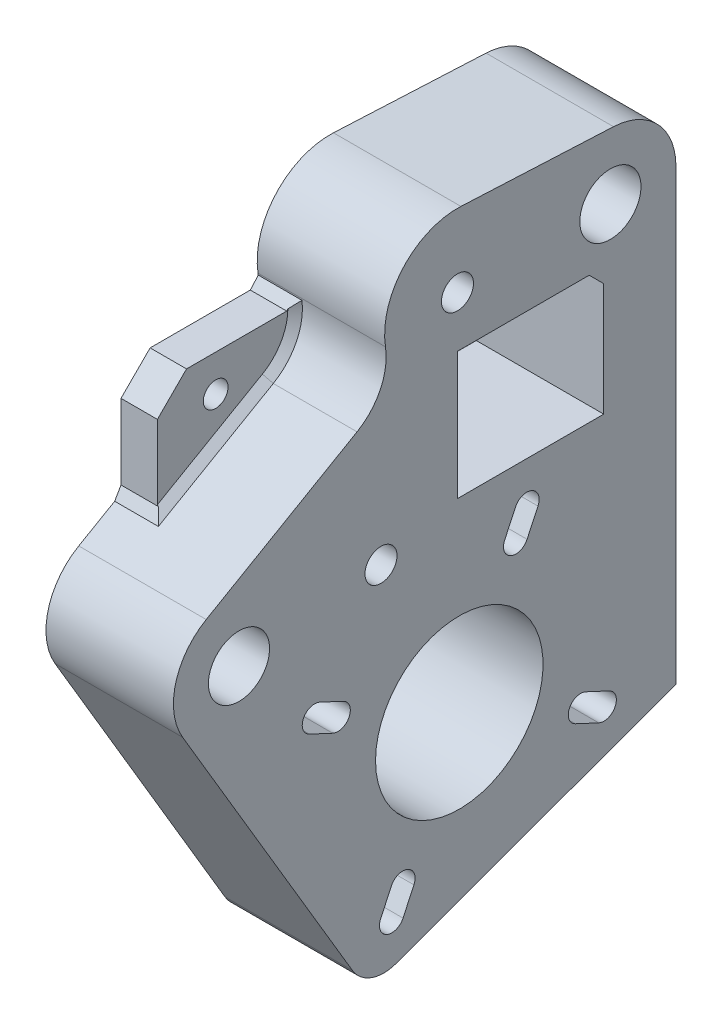
SolidWorks part; units mm, degrees
ref_plane "Front Plane" through (0, 0, 0) normal (0, 0, 1) x (1, 0, 0)
ref_plane "Top Plane" through (0, 0, 0) normal (0, 1, 0) x (1, 0, 0)
ref_plane "Right Plane" through (0, 0, 0) normal (1, 0, 0) x (0, 0, -1)
ref_plane "Plane1" through (0, 0, 0) normal (-1, 0, 0) x (0, -1, 0)
sketch "Sketch1" plane through (0, 0, 0) normal (-1, 0, 0) x (0, -1, 0)
  line L0 (11.2005, 72.3805) -> (-8.7575, 37.8123)
  line L1 (-24.9887, 29.5238) -> (-23.5812, 0)
  line L2 (-23.5812, 0) -> (46.6053, 0)
  line L3 (46.6053, 0) -> (62.0013, 42.3)
  line L4 (62.0013, 42.3) -> (11.2005, 72.3805)
  arc A0 (-8.7575, 37.8123) -> (-24.9887, 29.5238) centre (-15, 30) ccw
extrude "Boss-Extrude1" add sketch "Sketch1" against normal blind 17.5
sketch "Sketch2" plane through (0, 0, 0) normal (-1, 0, 0) x (0, -1, 0)
  line L0 (-8.7575, 37.8123) -> (3.302, 58.7)
  line L1 (3.302, 58.7) -> (-12, 58.7)
  line L2 (-12, 58.7) -> (-12, 39.5394)
  arc A0 (-12, 39.5394) -> (-8.7575, 37.8123) centre (-15, 30) cw
extrude "Boss-Extrude2" add sketch "Sketch2" against normal blind 5
sketch "Sketch3" plane through (0, 0, 0) normal (-1, 0, 0) x (0, 0, 1)
  line L0 (18.9442, -15.9372) -> (20.4384, -19.1415)
  line L1 (23.5198, -17.7046) -> (22.0256, -14.5003)
  arc A0 (20.4384, -19.1415) -> (23.5198, -17.7046) centre (21.9791, -18.423) ccw
  arc A1 (22.0256, -14.5003) -> (18.9442, -15.9372) centre (20.4849, -15.2188) ccw
extrude "Cut-Extrude1" cut sketch "Sketch3" against normal through all
sketch "Sketch4" plane through (0, 0, 0) normal (-1, 0, 0) x (0, 0, 1)
  line L0 (48.8969, -24.2807) -> (45.6927, -25.7748)
  line L1 (47.1296, -28.8563) -> (50.3338, -27.3621)
  arc A0 (50.3338, -27.3621) -> (48.8969, -24.2807) centre (49.6154, -25.8214) ccw
  arc A1 (45.6927, -25.7748) -> (47.1296, -28.8563) centre (46.4111, -27.3156) ccw
extrude "Cut-Extrude2" cut sketch "Sketch4" against normal through all
sketch "Sketch5" plane through (0, 0, 0) normal (-1, 0, 0) x (0, 0, 1)
  line L0 (35.9779, -52.466) -> (37.472, -55.6703)
  line L1 (40.5535, -54.2334) -> (39.0593, -51.0291)
  arc A0 (37.472, -55.6703) -> (40.5535, -54.2334) centre (39.0128, -54.9518) ccw
  arc A1 (39.0593, -51.0291) -> (35.9779, -52.466) centre (37.5186, -51.7476) ccw
extrude "Cut-Extrude3" cut sketch "Sketch5" against normal through all
sketch "Sketch6" plane through (0, 0, 0) normal (-1, 0, 0) x (0, 0, 1)
  line L0 (10.6007, -45.8899) -> (13.805, -44.3958)
  line L1 (12.3681, -41.3143) -> (9.1638, -42.8085)
  arc A0 (13.805, -44.3958) -> (12.3681, -41.3143) centre (13.0866, -42.855) ccw
  arc A1 (9.1638, -42.8085) -> (10.6007, -45.8899) centre (9.8823, -44.3492) ccw
extrude "Cut-Extrude4" cut sketch "Sketch6" against normal through all
sketch "Sketch7" plane through (17.5, 0, 0) normal (1, 0, 0) x (0, 0, -1)
  line L0 (-30, 7.9961) -> (-30, -9.5217)
  line L1 (-30, -9.5217) -> (-9.9147, -9.5217)
  line L3 (-9.9147, -9.5217) -> (-9.9147, 7.9961)
  line L4 (-9.9147, 7.9961) -> (-30, 7.9961)
  dimension "D1" = 17.5178
extrude "Cut-Extrude5" cut sketch "Sketch7" against normal through all
hole_wizard "Hole1" positions "Sketch9" profile "Sketch8" legacy
sketch "Sketch9" plane through (5, 0, 0) normal (1, 0, 0) x (0, 0, -1)
  point P0 (-50.7, 7)
sketch "Sketch8" plane through (5, 7, 50.7) normal (0, 1, 0) x (0, 0, -1)
  line L0 (0, 0) -> (0, 5)
  line L1 (0, 5) -> (1.7, 5)
  line L2 (1.7, 5) -> (1.7, 0)
  line L3 (1.7, 0) -> (0, 0)
  line L4 (0, 110) -> (0, -10) construction
  dimension "Diameter" = 3.4
  dimension "Depth" = 5
hole_wizard "Hole2" positions "Sketch11" profile "Sketch10" legacy
sketch "Sketch11" plane through (0, 0, 0) normal (-1, 0, 0) x (0, 0, 1)
  point P0 (9, 15)
sketch "Sketch10" plane through (0, 15, 9) normal (0, 1, 0) x (0, 0, 1)
  line L0 (0, 0) -> (0, 17.5)
  line L1 (0, 17.5) -> (4.2, 17.5)
  line L2 (4.2, 17.5) -> (4.2, 0)
  line L3 (4.2, 0) -> (0, 0)
  line L4 (0, 110) -> (0, -10) construction
  dimension "Diameter" = 8.4
  dimension "Depth" = 17.5
hole_wizard "Hole3" positions "Sketch13" profile "Sketch12" legacy
sketch "Sketch13" plane through (0, 0, 0) normal (-1, 0, 0) x (0, 0, 1)
  point P0 (40.5, -12.1507)
sketch "Sketch12" plane through (0, -12.1507, 40.5) normal (0, 1, 0) x (0, 0, 1)
  line L0 (0, 0) -> (0, 17.5)
  line L1 (0, 17.5) -> (2.2, 17.5)
  line L2 (2.2, 17.5) -> (2.2, 0)
  line L3 (2.2, 0) -> (0, 0)
  line L4 (0, 110) -> (0, -10) construction
  dimension "Diameter" = 4.4
  dimension "Depth" = 17.5
hole_wizard "Hole4" positions "Sketch15" profile "Sketch14" legacy
sketch "Sketch15" plane through (0, 0, 0) normal (-1, 0, 0) x (0, 0, 1)
  point P0 (29.7488, -35.0853)
sketch "Sketch14" plane through (0, -35.0853, 29.7488) normal (0, 1, 0) x (0, 0, 1)
  line L0 (0, 0) -> (0, 17.5)
  line L1 (0, 17.5) -> (11.5, 17.5)
  line L2 (11.5, 17.5) -> (11.5, 0)
  line L3 (11.5, 0) -> (0, 0)
  line L4 (0, 110) -> (0, -10) construction
  dimension "Diameter" = 23
  dimension "Depth" = 17.5
hole_wizard "Hole5" positions "Sketch17" profile "Sketch16" legacy
sketch "Sketch17" plane through (0, 0, 0) normal (-1, 0, 0) x (0, 0, 1)
  point P0 (60, -14.4449)
sketch "Sketch16" plane through (0, -14.4449, 60) normal (0, 1, 0) x (0, 0, 1)
  line L0 (0, 0) -> (0, 17.5)
  line L1 (0, 17.5) -> (4.2, 17.5)
  line L2 (4.2, 17.5) -> (4.2, 0)
  line L3 (4.2, 0) -> (0, 0)
  line L4 (0, 110) -> (0, -10) construction
  dimension "Diameter" = 8.4
  dimension "Depth" = 17.5
hole_wizard "Hole6" positions "Sketch19" profile "Sketch18" legacy
sketch "Sketch19" plane through (0, 0, 0) normal (-1, 0, 0) x (0, 0, 1)
  point P0 (30, 15)
sketch "Sketch18" plane through (0, 15, 30) normal (0, 1, 0) x (0, 0, 1)
  line L0 (0, 0) -> (0, 17.5)
  line L1 (0, 17.5) -> (2.2, 17.5)
  line L2 (2.2, 17.5) -> (2.2, 0)
  line L3 (2.2, 0) -> (0, 0)
  line L4 (0, 110) -> (0, -10) construction
  dimension "Diameter" = 4.4
  dimension "Depth" = 17.5
fillet "Fillet1" radius 8 1 edges at (11.25, 8.7575, 37.8123) tangent propagation no
chamfer "Chamfer1" distance 3.2893 angle 45 rebuild error yes
chamfer "Chamfer2" distance 1 angle 30 1 edges at (2.5, -3.302, 58.7) first distance on face at (7.5, -3.0647, 58.289)
chamfer "Chamfer3" distance 4 angle 45 1 edges at (2.5, 12, 58.7)
chamfer "Chamfer4" distance 2 angle 45 1 edges at (8.75, 7.9961, 9.9147)
chamfer "Chamfer5" distance 1.1548 angle 48.269 1 edges at (2.5, 12, 39.7901) first distance on face at (2.5, 12, 47.245)
chamfer "Chamfer6" distance 1 angle 45 2 edges at (5, 8.6749, 40.6231) (5, 0.7531, 51.6763)
fillet "Fillet2" radius 5 1 edges at (8.75, -62.0013, 42.3) tangent propagation no
fillet "Fillet3" radius 9 1 edges at (8.75, -11.2005, 72.3805) tangent propagation no
fillet "Fillet4" radius 9 1 edges at (8.75, 23.5812, 0)
